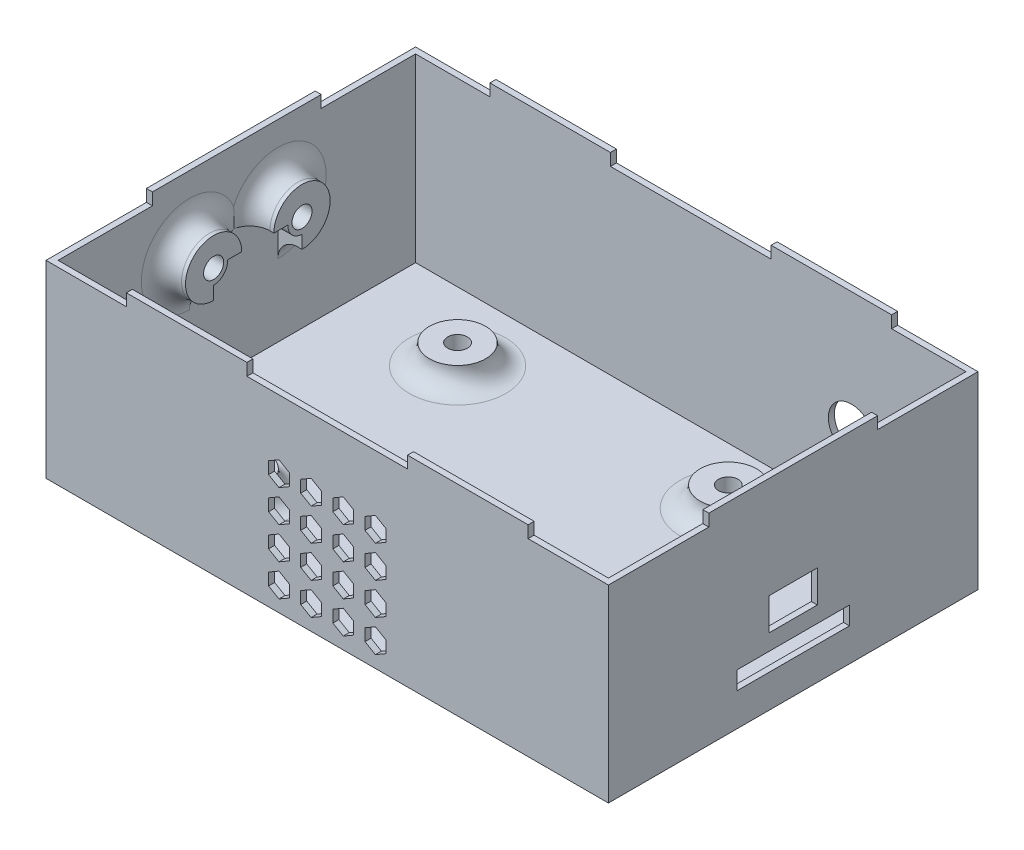
SolidWorks part; units mm, degrees
ref_plane "Front Plane" through (0, 0, 0) normal (0, 0, 1) x (1, 0, 0)
ref_plane "Top Plane" through (0, 0, 0) normal (0, 1, 0) x (1, 0, 0)
ref_plane "Right Plane" through (0, 0, 0) normal (1, 0, 0) x (0, 0, -1)
sketch "Sketch1" plane through (0, 0, 0) normal (0, 1, 0) x (1, 0, 0)
  line L1 (70, -46) -> (-70, -46)
  line L2 (70, -46) -> (70, 46)
  line L3 (70, 46) -> (-70, 46)
  line L4 (-70, -46) -> (-70, 46)
  line L5 (70, -46) -> (-70, 46) construction
  line L6 (70, 46) -> (-70, -46) construction
  line L12 (38, 12.25) -> (80, 12.25)
  line L13 (38, 12.25) -> (38, -12.25)
  line L14 (38, -12.25) -> (80, -12.25)
  line L15 (80, 12.25) -> (80, -12.25)
  line L16 (38, 12.25) -> (80, -12.25) construction
  line L17 (38, -12.25) -> (80, 12.25) construction
  line L22 (68.5, -44.5) -> (-68.5, -44.5)
  line L23 (68.5, -44.5) -> (68.5, 44.5)
  line L24 (68.5, 44.5) -> (-68.5, 44.5)
  line L25 (-68.5, -44.5) -> (-68.5, 44.5)
  line L26 (68.5, -44.5) -> (-68.5, 44.5) construction
  line L27 (68.5, 44.5) -> (-68.5, -44.5) construction
  circle A0 centre (-41.0549, 27.5) radius 7
  circle A1 centre (-41.0549, -27) radius 7
  circle A2 centre (23.3451, 30.5) radius 7
  circle A6 centre (40, -10.25) radius 3.5
  circle A7 centre (40, 10.25) radius 3.5
  point P0 (0, 0)
  point P6 (0, 0)
  point P9 (0, 0)
  point P22 (59, 0)
  dimension "D7" = 14
  dimension "D8" = 14
  dimension "D5" = 3
  dimension "D11" = 14
  dimension "D25" = 7
  dimension "D27" = 7
  dimension "D13" = 35.75
  dimension "D9" = 17
  dimension "D1" = 140
  dimension "D3" = 64.4
  dimension "D4" = 54.5
  dimension "D6" = 0
  dimension "D10" = 92
  dimension "D12" = 1.5
  dimension "D14" = 28.9451
  dimension "D19" = 30
  dimension "D20" = 20.5
  dimension "D21" = 10
  dimension "D23" = 2
  dimension "D24" = 1.5
  dimension "D26" = 2
  dimension "D28" = 2
  dimension "D29" = 30
extrude "Boss-Extrude2" add sketch "Sketch1" along normal blind 7 contours A2 | A0 | A1 | A6 | A7 region at (-41.0549, 0, -27.5) region at (-41.0549, 0, 27) region at (23.3451, 0, -30.5)
sketch "Sketch3" plane through (0, 0, 0) normal (0, 1, 0) x (1, 0, 0)
  line L1 (-70, -46) -> (70, -46)
  line L2 (-70, -46) -> (-70, 46)
  line L3 (-70, 46) -> (70, 46)
  line L4 (70, -46) -> (70, 46)
  line L5 (-70, -46) -> (70, 46) construction
  line L6 (-70, 46) -> (70, -46) construction
  point P0 (0, 0)
  dimension "D1" = 92
  dimension "D2" = 140
extrude "Boss-Extrude3" add sketch "Sketch3" along normal blind 2
sketch "Sketch4" plane through (0, 2, 0) normal (0, 1, 0) x (1, 0, 0)
  line L0 (70, 46) -> (-70, 46) construction
  line L1 (68.5, -44.5) -> (-68.5, -44.5)
  line L2 (68.5, -44.5) -> (68.5, 44.5)
  line L3 (68.5, 44.5) -> (-68.5, 44.5)
  line L4 (-68.5, -44.5) -> (-68.5, 44.5)
  line L5 (68.5, -44.5) -> (-68.5, 44.5) construction
  line L6 (68.5, 44.5) -> (-68.5, -44.5) construction
  line L7 (-70, 46) -> (-70, -46) construction
  line L9 (70, -46) -> (-70, -46)
  line L10 (70, -46) -> (70, 46)
  line L11 (70, 46) -> (-70, 46)
  line L12 (-70, -46) -> (-70, 46)
  line L13 (70, -46) -> (-70, 46) construction
  line L14 (70, 46) -> (-70, -46) construction
  point P0 (0, 0)
  point P10 (0, 0)
  dimension "D1" = 1.5
  dimension "D2" = 1.5
extrude "Boss-Extrude4" add sketch "Sketch4" along normal blind 45
sketch "Sketch5" plane through (0, 7, 0) normal (0, 1, 0) x (1, 0, 0)
  circle A0 centre (23.3451, 30.5) radius 2.45
  circle A1 centre (-41.0549, 27.5) radius 2.45
  circle A2 centre (-41.0549, -27) radius 2.45
  dimension "D1" = 4.9
  dimension "D4" = 4.9
  dimension "D5" = 4.9
extrude "Cut-Extrude1" cut sketch "Sketch5" against normal blind 5.1
sketch "Sketch6" plane through (0, 7, 0) normal (0, 1, 0) x (1, 0, 0)
  circle A0 centre (40, 10.25) radius 1
  circle A1 centre (40, -10.25) radius 1
  dimension "D1" = 2
  dimension "D2" = 2
extrude "Cut-Extrude2" cut sketch "Sketch6" against normal blind 5.1
sketch "Sketch7" plane through (-68.5, 0, 0) normal (1, 0, 0) x (0, 0, -1)
  line L0 (44.5, 2) -> (-44.5, 2) construction
  circle A0 centre (-11.7728, 32) radius 7
  circle A1 centre (10.2272, 32) radius 7
  dimension "D2" = 14
  dimension "D3" = 14
  dimension "D1" = 22
  dimension "D4" = 30
extrude "Boss-Extrude5" add sketch "Sketch7" along normal blind 6
sketch "Sketch8" plane through (-62.5, 0, 0) normal (1, 0, 0) x (0, 0, -1)
  circle A0 centre (-11.7728, 32) radius 2.5
  circle A1 centre (10.2272, 32) radius 2.5
  dimension "D1" = 5
  dimension "D2" = 5
extrude "Cut-Extrude3" cut sketch "Sketch8" against normal blind 5.1
sketch "Sketch9" plane through (0, 47, 0) normal (0, 1, 0) x (1, 0, 0)
  line L0 (-68.5, -44.5) -> (68.5, -44.5) construction
  line L1 (-50, -44.5) -> (-20, -44.5)
  line L2 (-50, -44.5) -> (-50, -46)
  line L3 (-50, -46) -> (-20, -46)
  line L4 (-20, -44.5) -> (-20, -46)
  line L5 (-70, -46) -> (70, -46) construction
  line L6 (-68.5, -44.5) -> (68.5, -44.5) construction
  line L7 (20, -44.5) -> (50, -44.5)
  line L8 (20, -44.5) -> (20, -46)
  line L9 (20, -46) -> (50, -46)
  line L10 (50, -44.5) -> (50, -46)
  line L11 (-70, 46) -> (-70, -46) construction
  line L12 (70, -46) -> (70, 46) construction
  line L13 (68.5, -44.5) -> (68.5, 44.5) construction
  line L18 (68.5, 21) -> (70, 21)
  line L19 (68.5, 21) -> (68.5, -21)
  line L20 (68.5, -21) -> (70, -21)
  line L21 (-68.5, 44.5) -> (-68.5, -44.5) construction
  line L22 (-68.5, -21) -> (-70, -21)
  line L23 (-68.5, -21) -> (-68.5, 21)
  line L24 (-68.5, 21) -> (-70, 21)
  line L25 (-70, -21) -> (-70, 21)
  line L26 (70, 46) -> (-70, 46) construction
  line L27 (70, 21) -> (70, -21)
  line L28 (68.5, 44.5) -> (-68.5, 44.5) construction
  line L29 (20, 44.5) -> (50, 44.5)
  line L30 (20, 44.5) -> (20, 46)
  line L31 (20, 46) -> (50, 46)
  line L32 (50, 44.5) -> (50, 46)
  line L34 (-50, 44.5) -> (-20, 44.5)
  line L35 (-50, 44.5) -> (-50, 46)
  line L36 (-50, 46) -> (-20, 46)
  line L37 (-20, 44.5) -> (-20, 46)
  dimension "D1" = 20
  dimension "D2" = 20
  dimension "D3" = 30
  dimension "D4" = 30
  dimension "D5" = 25
  dimension "D6" = 25
  dimension "D7" = 20
  dimension "D8" = 20
  dimension "D9" = 30
  dimension "D10" = 30
  dimension "D11" = 25
  dimension "D12" = 25
extrude "Boss-Extrude6" add sketch "Sketch9" along normal blind 3
sketch "Sketch11" plane through (70, 0, 0) normal (1, 0, 0) x (0, 0, -1)
  line L0 (-46, 0) -> (46, 0) construction
  line L1 (-14, 8.2) -> (14, 8.2)
  line L2 (-14, 8.2) -> (-14, 12.7)
  line L3 (-14, 12.7) -> (14, 12.7)
  line L4 (14, 8.2) -> (14, 12.7)
  line L5 (-46, 47) -> (-46, 0) construction
  line L7 (46, 47) -> (46, 0) construction
  dimension "D1" = 8.2
  dimension "D2" = 32
  dimension "D3" = 32
  dimension "D4" = 4.5
sketch "Sketch12" plane through (0, 7, 0) normal (0, 1, 0) x (1, 0, 0)
  circle A0 centre (40, 10.25) radius 3.5
  circle A1 centre (40, -10.25) radius 3.5
  circle A2 centre (40, 10.25) radius 1
  circle A3 centre (40, -10.25) radius 1
  dimension "D1" = 2
  dimension "D2" = 7
  dimension "D3" = 2
  dimension "D4" = 7
extrude "Boss-Extrude7" add sketch "Sketch12" along normal blind 2
extrude "Cut-Extrude4" cut sketch "Sketch11" against normal up to next
sketch "Sketch14" plane through (0, 0, -46) normal (0, 0, -1) x (-1, 0, 0)
  line L0 (-70, 47) -> (-70, 0) construction
  line L1 (-70, 0) -> (70, 0) construction
  circle A0 centre (-40, 20) radius 5.75
  dimension "D1" = 30
  dimension "D3" = 11.5
  dimension "D2" = 20
extrude "Cut-Extrude5" cut sketch "Sketch14" against normal up to next
sketch "Sketch15" plane through (0, 0, 46) normal (0, 0, 1) x (1, 0, 0)
  line L98 (-4.0006, 9) -> (-6.5987, 7.5)
  line L297 (-12.0019, 9) -> (-14.6, 7.5)
  line L299 (-14.6, 7.5) -> (-14.6, 4.5)
  line L301 (-14.6, 4.5) -> (-12.0019, 3)
  line L302 (-12.0019, 3) -> (-9.4038, 4.5)
  line L307 (-9.4038, 4.5) -> (-9.4038, 7.5)
  line L308 (-9.4038, 7.5) -> (-12.0019, 9)
  line L309 (-6.5987, 7.5) -> (-6.5987, 4.5)
  line L310 (-6.5987, 4.5) -> (-4.0006, 3)
  line L311 (-4.0006, 3) -> (-1.4026, 4.5)
  line L312 (-1.4026, 4.5) -> (-1.4026, 7.5)
  line L313 (-1.4026, 7.5) -> (-4.0006, 9)
  line L314 (4.0006, 9) -> (1.4026, 7.5)
  line L315 (1.4026, 7.5) -> (1.4026, 4.5)
  line L316 (1.4026, 4.5) -> (4.0006, 3)
  line L317 (4.0006, 3) -> (6.5987, 4.5)
  line L318 (6.5987, 4.5) -> (6.5987, 7.5)
  line L319 (6.5987, 7.5) -> (4.0006, 9)
  line L320 (12.0019, 9) -> (9.4038, 7.5)
  line L321 (9.4038, 7.5) -> (9.4038, 4.5)
  line L322 (9.4038, 4.5) -> (12.0019, 3)
  line L323 (12.0019, 3) -> (14.6, 4.5)
  line L324 (14.6, 4.5) -> (14.6, 7.5)
  line L325 (14.6, 7.5) -> (12.0019, 9)
  line L326 (-4.0006, 17) -> (-6.5987, 15.5)
  line L327 (-6.5987, 15.5) -> (-6.5987, 12.5)
  line L328 (-6.5987, 12.5) -> (-4.0006, 11)
  line L329 (-4.0006, 11) -> (-1.4026, 12.5)
  line L330 (-1.4026, 12.5) -> (-1.4026, 15.5)
  line L331 (-1.4026, 15.5) -> (-4.0006, 17)
  line L332 (4.0007, 17) -> (1.4026, 15.5)
  line L333 (1.4026, 15.5) -> (1.4026, 12.5)
  line L334 (1.4026, 12.5) -> (4.0007, 11)
  line L335 (4.0007, 11) -> (6.5987, 12.5)
  line L336 (6.5987, 12.5) -> (6.5987, 15.5)
  line L337 (6.5987, 15.5) -> (4.0007, 17)
  line L338 (12.0019, 17) -> (9.4039, 15.5)
  line L339 (9.4039, 15.5) -> (9.4039, 12.5)
  line L340 (9.4039, 12.5) -> (12.0019, 11)
  line L341 (12.0019, 11) -> (14.6, 12.5)
  line L342 (14.6, 12.5) -> (14.6, 15.5)
  line L343 (14.6, 15.5) -> (12.0019, 17)
  line L344 (-4.0006, 25) -> (-6.5987, 23.5)
  line L345 (-6.5987, 23.5) -> (-6.5987, 20.5)
  line L346 (-6.5987, 20.5) -> (-4.0006, 19)
  line L347 (-4.0006, 19) -> (-1.4025, 20.5)
  line L348 (-1.4025, 20.5) -> (-1.4025, 23.5)
  line L349 (-1.4025, 23.5) -> (-4.0006, 25)
  line L350 (4.0007, 25) -> (1.4026, 23.5)
  line L351 (1.4026, 23.5) -> (1.4026, 20.5)
  line L352 (1.4026, 20.5) -> (4.0007, 19)
  line L353 (4.0007, 19) -> (6.5987, 20.5)
  line L354 (6.5987, 20.5) -> (6.5987, 23.5)
  line L355 (6.5987, 23.5) -> (4.0007, 25)
  line L356 (12.0019, 25) -> (9.4039, 23.5)
  line L357 (9.4039, 23.5) -> (9.4039, 20.5)
  line L358 (9.4039, 20.5) -> (12.0019, 19)
  line L359 (12.0019, 19) -> (14.6, 20.5)
  line L360 (14.6, 20.5) -> (14.6, 23.5)
  line L361 (14.6, 23.5) -> (12.0019, 25)
  line L362 (-4.0006, 33) -> (-6.5987, 31.5)
  line L363 (-6.5987, 31.5) -> (-6.5987, 28.5)
  line L364 (-6.5987, 28.5) -> (-4.0006, 27)
  line L365 (-4.0006, 27) -> (-1.4025, 28.5)
  line L366 (-1.4025, 28.5) -> (-1.4025, 31.5)
  line L367 (-1.4025, 31.5) -> (-4.0006, 33)
  line L368 (4.0007, 33) -> (1.4026, 31.5)
  line L369 (1.4026, 31.5) -> (1.4026, 28.5)
  line L370 (1.4026, 28.5) -> (4.0007, 27)
  line L371 (4.0007, 27) -> (6.5987, 28.5)
  line L372 (6.5987, 28.5) -> (6.5987, 31.5)
  line L373 (6.5987, 31.5) -> (4.0007, 33)
  line L374 (12.002, 33) -> (9.4039, 31.5)
  line L375 (9.4039, 31.5) -> (9.4039, 28.5)
  line L376 (9.4039, 28.5) -> (12.002, 27)
  line L377 (12.002, 27) -> (14.6, 28.5)
  line L378 (14.6, 28.5) -> (14.6, 31.5)
  line L379 (14.6, 31.5) -> (12.002, 33)
  line L380 (-12.0019, 17) -> (-14.6, 15.5)
  line L381 (-14.6, 15.5) -> (-14.6, 12.5)
  line L382 (-14.6, 12.5) -> (-12.0019, 11)
  line L383 (-12.0019, 11) -> (-9.4038, 12.5)
  line L384 (-9.4038, 12.5) -> (-9.4038, 15.5)
  line L385 (-9.4038, 15.5) -> (-12.0019, 17)
  line L386 (-12.0019, 25) -> (-14.6, 23.5)
  line L387 (-14.6, 23.5) -> (-14.6, 20.5)
  line L388 (-14.6, 20.5) -> (-12.0019, 19)
  line L389 (-12.0019, 19) -> (-9.4038, 20.5)
  line L390 (-9.4038, 20.5) -> (-9.4038, 23.5)
  line L391 (-9.4038, 23.5) -> (-12.0019, 25)
  line L392 (-12.0019, 33) -> (-14.6, 31.5)
  line L393 (-14.6, 31.5) -> (-14.6, 28.5)
  line L394 (-14.6, 28.5) -> (-12.0019, 27)
  line L395 (-12.0019, 27) -> (-9.4038, 28.5)
  line L396 (-9.4038, 28.5) -> (-9.4038, 31.5)
  line L397 (-9.4038, 31.5) -> (-12.0019, 33)
  line L398 (-70, 47) -> (-70, 0) construction
  line L401 (-70, 0) -> (70, 0) construction
  circle A4 centre (-12.0019, 6) radius 2.5981 construction
  dimension "D3" = 55.4
  dimension "D4" = 6
  dimension "D7" = 8.0013
  dimension "D1" = 4
  dimension "D2" = 4
extrude "Cut-Extrude7" cut sketch "Sketch15" against normal up to next
fillet "Fillet1" radius 5 7 edges at (-41.0549, 2, 20) (40, 2, -13.75) (40, 2, 6.75) (-41.0549, 2, -34.5) (-68.5, 32, 4.7728) (-68.5, 32, -17.2272) (23.3451, 2, -37.5)
sketch "Sketch16" plane through (-62.5, 0, 0) normal (1, 0, 0) x (0, 0, -1)
  line L8 (-8.2728, 32) -> (6.7272, 32)
  line L11 (-11.7728, 18.25) -> (10.2272, 18.25)
  line L13 (-11.7728, 28.25) -> (-11.7728, 18.25)
  line L14 (10.2272, 28.25) -> (10.2272, 18.25)
  arc A10 (-11.7728, 28.25) -> (-8.2728, 32) centre (-11.8978, 31.875) ccw
  arc A11 (6.7272, 32) -> (10.2272, 28.25) centre (10.3522, 31.875) ccw
  point P0 (0, 0)
extrude "Cut-Extrude8" cut sketch "Sketch16" against normal up to surface (6 mm away) contours A11 L14 L11 L13 A10 L8 up to face at (-68.5, 32, -0.5268)
sketch "Sketch17" plane through (70, 0, 0) normal (1, 0, 0) x (0, 0, -1)
  line L0 (14, 12.7) -> (-14, 12.7) construction
  line L1 (6, 16.7) -> (-6, 16.7)
  line L2 (6, 16.7) -> (6, 24.7)
  line L3 (6, 24.7) -> (-6, 24.7)
  line L4 (-6, 16.7) -> (-6, 24.7)
  line L5 (6, 16.7) -> (-6, 24.7) construction
  line L6 (6, 24.7) -> (-6, 16.7) construction
  line L8 (-46, 47) -> (-46, 0) construction
  line L9 (46, 47) -> (46, 0) construction
  point P0 (0, 20.7)
  dimension "D1" = 4
  dimension "D2" = 40
  dimension "D3" = 40
  dimension "D4" = 8
extrude "Cut-Extrude9" cut sketch "Sketch17" against normal up to next
